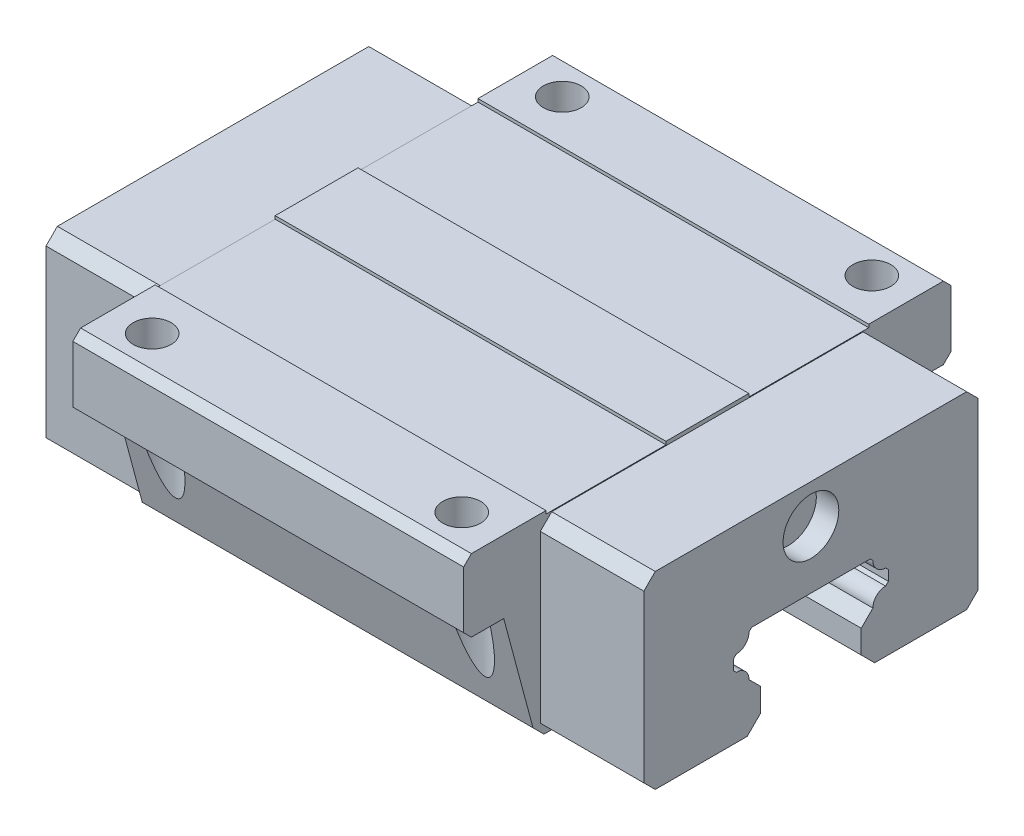
SolidWorks part; units mm, degrees
material "1060 Alloy"
ref_plane "Front Plane" through (0, 0, 0) normal (0, 0, 1) x (1, 0, 0)
ref_plane "Top Plane" through (0, 0, 0) normal (0, 1, 0) x (1, 0, 0)
ref_plane "Right Plane" through (0, 0, 0) normal (1, 0, 0) x (0, 0, -1)
sketch "Sketch2" plane through (0, 0, 0) normal (1, 0, 0) x (0, 0, -1)
  line L0 (0, 22.5899) -> (0, 0.5499) construction
  line L1 (-9.6464, -1.0186) -> (-9.6464, -2.6614) construction
  line L2 (-9.6464, -2.6614) -> (-8.0036, -2.6614) construction
  line L3 (-10, 0) -> (0, 0) construction
  line L4 (20.2658, -14.5) -> (-12.926, -14.5) construction
  line L8 (-8.235, -8.9) -> (-20.12, -8.9)
  line L9 (-20.12, -8.9) -> (-21.59, -7.43)
  line L10 (-21.59, -7.43) -> (-21.59, 14.03)
  line L11 (-21.59, 14.03) -> (-20.12, 15.5)
  line L12 (-20.12, 15.5) -> (0, 15.5)
  line L13 (-20.12, 15.5) -> (-20.12, -8.9) construction
  line L14 (0, 15.5) -> (0, 3.015)
  line L17 (-6.5, -7.165) -> (-8.235, -8.9)
  line L18 (-6.5, -4.165) -> (-6.5, -7.165)
  line L19 (-8.0036, -2.6614) -> (-6.5, -4.165)
  line L20 (-10, -0.665) -> (-9.6464, -1.0186)
  line L21 (-10, 0.665) -> (-10, -0.665)
  line L22 (-9.6464, 1.0186) -> (-10, 0.665)
  line L23 (-7.65, 3.015) -> (-8.0036, 2.6614)
  line L24 (0, 3.015) -> (-7.65, 3.015)
  line L25 (-8.0036, 2.6614) -> (-9.6464, 1.0186) construction
  line L26 (-9.6464, -1.0186) -> (-8.0036, -2.6614) construction
  line L27 (-8.0036, 2.6614) -> (-9.6464, 2.6614) construction
  line L28 (-9.6464, 2.6614) -> (-9.6464, 1.0186) construction
  arc A2 (-8.0036, -2.6614) -> (-9.6464, -1.0186) centre (-9.6464, -2.6614) ccw
  arc A3 (-9.6464, 1.0186) -> (-8.0036, 2.6614) centre (-9.6464, 2.6614) ccw
  point P4 (-10, 0)
  point P5 (-23.309, 31.262)
  dimension "D2" = 0.5
  dimension "D3" = 10
  dimension "D4" = 45
  dimension "D5" = 1.33
  dimension "D6" = 30
  dimension "D7" = 7.65
  dimension "D8" = 3
  dimension "D9" = 21.59
  dimension "D10" = 1.47
  dimension "D11" = 21.46
  dimension "D12" = 45
  dimension "D13" = 6.5
  dimension "D14" = 24.4
  dimension "D15" = 14.5
extrude "Boss-Extrude1" add sketch "Sketch2" along normal blind 38.63
sketch "Sketch3" plane through (0, 0, 0) normal (1, 0, 0) x (0, 0, -1)
  line L0 (-20.12, -8.9) -> (-21.12, -8.9)
  line L1 (-21.12, -8.9) -> (-22.5342, -7.4858)
  line L2 (-22.5342, -7.4858) -> (-26.3203, 6.6442)
  line L3 (-26.3203, 6.6442) -> (-31.5, 6.6442)
  line L4 (-31.5, 6.6442) -> (-31.5, 16)
  line L5 (-31.5, 16) -> (-20.855, 16)
  line L6 (-20.855, 16) -> (-20.855, 15.6)
  line L7 (-20.855, 15.6) -> (-5.355, 15.6)
  line L8 (-5.355, 15.6) -> (-5.355, 16)
  line L9 (-5.355, 16) -> (0, 16)
  line L10 (0, 16) -> (0, 15.5)
  line L11 (0, 15.5) -> (-20.12, 15.5)
  line L12 (-20.12, 15.5) -> (-21.59, 14.03)
  line L13 (-21.59, 14.03) -> (-21.59, -7.43)
  line L14 (-21.59, -7.43) -> (-20.12, -8.9)
  line L15 (-22.5342, -7.4858) -> (-30.0907, -7.4858) construction
  line L16 (-20.855, 15.6) -> (-20.855, 14.765) construction
  line L17 (-20.855, 16) -> (-5.355, 16) construction
  line L18 (0, 3.015) -> (0, 15.5) construction
  dimension "D1" = 1
  dimension "D2" = 45
  dimension "D3" = 2
  dimension "D4" = 75
  dimension "D5" = 14.13
  dimension "D6" = 31.5
  dimension "D7" = 0.5
  dimension "D8" = 0.1
  dimension "D9" = 15.5
extrude "Boss-Extrude2" add sketch "Sketch3" along normal offset from surface (25.25 mm away) 13.38 up to face at (38.63, 0.9063, 10.4328)
chamfer "Chamfer1" distance 1 angle 45 2 edges at (12.625, 6.6442, 31.5) (12.625, 16, 31.5)
sketch "Sketch4" plane through (0, 16, 0) normal (0, 1, 0) x (1, 0, 0)
  line L0 (20, -26.5) -> (25.25, -26.5) construction
  line L1 (25.25, -20.855) -> (25.25, -30.5) construction
  line L2 (20, -26.5) -> (20, -31.5) construction
  line L3 (25.25, -31.5) -> (0, -31.5) construction
  line L4 (25.25, 0) -> (0, 0) construction
  circle A0 centre (20, -26.5) radius 2.45
  dimension "D1" = 4.9
  dimension "D2" = 26.5
  dimension "D3" = 5.25
extrude "Cut-Extrude1" cut sketch "Sketch4" against normal through all
sketch "Sketch5" plane through (0, 16, 0) normal (0, 1, 0) x (1, 0, 0)
  circle A0 centre (20, -26.5) radius 3
  dimension "D1" = 6
extrude "Cut-Extrude2" cut sketch "Sketch5" against normal through all from offset 8.5 offset against normal yes
mirror "Mirror1" about plane through (0, 0, 0) normal (0, 0, 1) of bodies 104 110
sketch "Sketch12" plane through (38.63, 0, 0) normal (1, 0, 0) x (0, 0, -1)
  line L0 (0, 10.5) -> (0, 0) construction
  line L1 (-20.12, 15.5) -> (20.12, 15.5) construction
  circle A0 centre (0, 10.5) radius 3.6
  dimension "D1" = 7.2
  dimension "D2" = 5
extrude "Cut-Extrude8" cut sketch "Sketch12" against normal blind 2.9
mirror "Mirror2" about plane through (0, 0, 0) normal (1, 0, 0) of bodies 112 113
